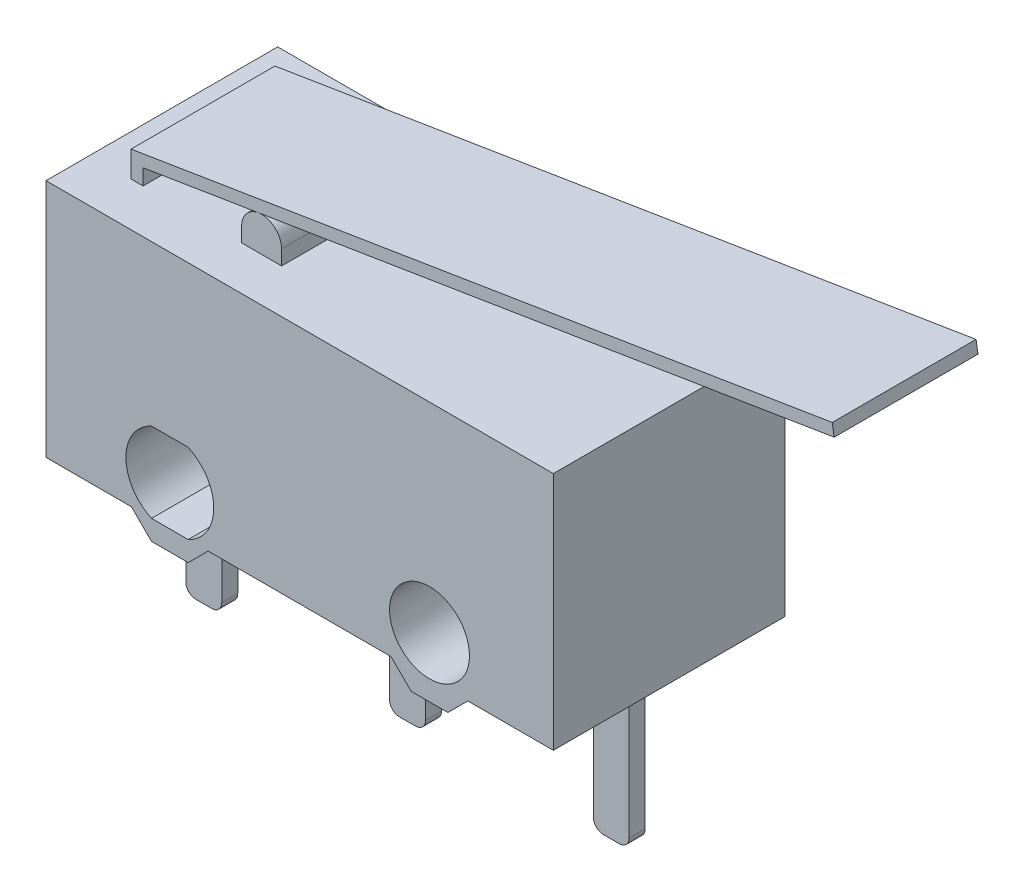
SolidWorks part; units mm, degrees
ref_plane "前视基准面" through (0, 0, 0) normal (0, 0, 1) x (1, 0, 0)
ref_plane "上视基准面" through (0, 0, 0) normal (0, 1, 0) x (1, 0, 0)
ref_plane "右视基准面" through (0, 0, 0) normal (1, 0, 0) x (0, 0, -1)
sketch "Sketch8" plane through (0, 0, 0) normal (0, 0, 1) x (1, 0, 0)
  line L0 (-0.0898, 5.1607) -> (-0.0898, -3) construction
  line L1 (-6.4398, 5.1607) -> (6.2602, 5.1607)
  line L2 (-6.4398, 5.1607) -> (-6.4398, -0.8393)
  line L3 (-6.4398, -0.8393) -> (-4.3001, -0.8393)
  line L4 (6.2602, 5.1607) -> (6.2602, -0.8393)
  line L5 (-3.798, 1.1607) -> (-2.8815, 1.1607)
  line L6 (-3.8001, -1.3393) -> (-2.8794, -1.3393)
  line L7 (-2.8794, -1.3393) -> (-2.3794, -0.8393)
  line L8 (-3.3398, -0.8393) -> (-3.3398, -1.3393) construction
  line L9 (-3.8001, -1.3393) -> (-4.3001, -0.8393)
  line L10 (2.6999, -1.3393) -> (2.1999, -0.8393)
  line L11 (3.6206, -1.3393) -> (2.6999, -1.3393)
  line L12 (3.6206, -1.3393) -> (4.1206, -0.8393)
  line L13 (-3.798, -0.8393) -> (-2.8815, -0.8393)
  line L14 (-2.3794, -0.8393) -> (2.1999, -0.8393)
  line L15 (4.1206, -0.8393) -> (6.2602, -0.8393)
  line L16 (4.5602, -0.8393) -> (5.4602, -0.8393)
  line L17 (-4.9898, -4.7393) -> (-5.3898, -4.7393)
  line L18 (-4.7398, -4.4893) -> (-4.7398, -0.8393)
  line L19 (-4.7398, -0.8393) -> (-5.6398, -0.8393)
  line L20 (-5.6398, -4.4893) -> (-5.6398, -0.8393)
  line L21 (-4.7398, -4.7393) -> (-5.6398, -0.8393) construction
  line L22 (-4.7398, -0.8393) -> (-5.6398, -4.7393) construction
  line L23 (5.4602, -4.4893) -> (5.4602, -0.8393)
  line L24 (4.8102, -4.7393) -> (5.2102, -4.7393)
  line L25 (4.5602, -4.4893) -> (4.5602, -0.8393)
  line L27 (0.1102, -4.7393) -> (-0.2898, -4.7393)
  line L28 (0.3602, -4.4893) -> (0.3602, -0.8393)
  line L29 (0.3602, -0.8393) -> (-0.5398, -0.8393)
  line L30 (-0.5398, -4.4893) -> (-0.5398, -0.8393)
  line L31 (0.3602, -4.7393) -> (-0.5398, -0.8393) construction
  line L32 (0.3602, -0.8393) -> (-0.5398, -4.7393) construction
  arc A0 (-3.798, 1.1607) -> (-3.798, -0.8393) centre (-3.3398, 0.1607) ccw
  circle A1 centre (3.1602, 0.1607) radius 1
  arc A2 (-2.8815, -0.8393) -> (-2.8815, 1.1607) centre (-3.3398, 0.1607) ccw
  arc A3 (5.4602, -4.4893) -> (5.2102, -4.7393) centre (5.2102, -4.4893) cw
  arc A4 (4.8102, -4.7393) -> (4.5602, -4.4893) centre (4.8102, -4.4893) cw
  arc A5 (0.1102, -4.7393) -> (0.3602, -4.4893) centre (0.1102, -4.4893) ccw
  arc A6 (-0.2898, -4.7393) -> (-0.5398, -4.4893) centre (-0.2898, -4.4893) cw
  arc A7 (-4.9898, -4.7393) -> (-4.7398, -4.4893) centre (-4.9898, -4.4893) ccw
  arc A8 (-5.3898, -4.7393) -> (-5.6398, -4.4893) centre (-5.3898, -4.4893) cw
  point P0 (0, 0)
  point P25 (-5.1898, -2.7893)
  point P34 (-0.0898, -2.7893)
  point P41 (5.4602, -4.7393)
  point P44 (4.5602, -4.7393)
  dimension "D3" = 1
  dimension "D8" = 2.2
  dimension "D14" = 0.25
  dimension "D1" = 12.7
  dimension "D2" = 6
  dimension "D4" = 1
  dimension "D5" = 3.25
  dimension "D6" = 3.25
  dimension "D7" = 1
  dimension "D9" = 0.5
  dimension "D10" = 0.9
  dimension "D11" = 5.1
  dimension "D12" = 3.9
  dimension "D13" = 0.9
extrude "Boss-Extrude10" add sketch "Sketch8" along normal mid plane 5.8 contours L12 L15 L4 L1 L2 L3 L9 L6 L7 L14 L10 L11 A2 L13 A0 L5 A1 region at (-0.0651, 2.2887, 0)
extrude "Boss-Extrude11" add sketch "Sketch8<3>" along normal mid plane 0.4 contours L20 L17 L18 L3 | L30 L27 L28 L14 | L25 L24 L23 L15 region at (-5.1898, -2.7747, 0) region at (5.0102, -2.7747, 0) region at (-0.0898, -2.7747, 0)
sketch "Sketch8<3>" plane through (0, 0, 0) normal (0, 0, 1) x (1, 0, 0) same geometry as "Sketch8"
sketch "Sketch9" plane through (0, 0, 0) normal (0, 0, 1) x (1, 0, 0)
  line L0 (-5.41, 5.1607) -> (-5.41, 5.5797)
  line L1 (-6.4398, 5.1607) -> (6.2602, 5.1607) construction
  line L5 (-5.11, 5.3164) -> (-5.11, 5.1607)
  line L6 (-5.11, 5.1607) -> (-5.41, 5.1607)
  line L8 (4.3557, 8.6607) -> (10.6651, 8.6607) construction
  line L9 (4.1206, -0.8393) -> (6.2602, -0.8393) construction
  line L10 (3.4567, 11.1607) -> (15.6341, 11.1607) construction
  line L11 (11.5602, 11.7825) -> (11.5602, 4.6537) construction
  line L12 (-6.4398, 5.1607) -> (-6.4398, -0.8393) construction
  line L14 (-5.41, 5.8102) -> (-5.41, 5.5797)
  line L15 (11.5602, 11.1607) -> (11.6505, 10.8746)
  line L16 (-2.0141, 5.1607) -> (-2.2654, 5.1607)
  line L17 (-5.41, 5.8102) -> (12.1424, 8.6607)
  line L18 (12.1424, 8.6607) -> (12.1905, 8.3646)
  line L19 (12.1905, 8.3646) -> (-5.11, 5.5549)
  line L20 (-5.11, 5.5549) -> (-5.11, 5.3164)
  line L24 (-0.3905, 6.0607) -> (-1.6097, 6.0607) construction
  line L25 (-2.6419, 5.5304) -> (-2.6419, 5.1607)
  line L26 (-2.6419, 5.1607) -> (-1.6419, 5.1607)
  line L27 (-1.6419, 5.1607) -> (-1.6419, 5.5304)
  arc A0 (-1.6419, 5.5304) -> (-2.6419, 5.5304) centre (-2.1419, 5.5304) ccw
  dimension "D8" = 0.9
  dimension "D1" = 0.3
  dimension "D2" = 9.5
  dimension "D3" = 12
  dimension "D4" = 18
  dimension "D5" = 0.3
  dimension "D6" = 0.3
extrude "Boss-Extrude13" add sketch "Sketch9" along normal mid plane 3.6 separate body contours L27 A0 L25 L26 L16 | L20 L19 L18 L17 L14 L0 L6 L5 region at (-2.1419, 5.5501, 0) region at (3.2025, 7.0499, 0)
